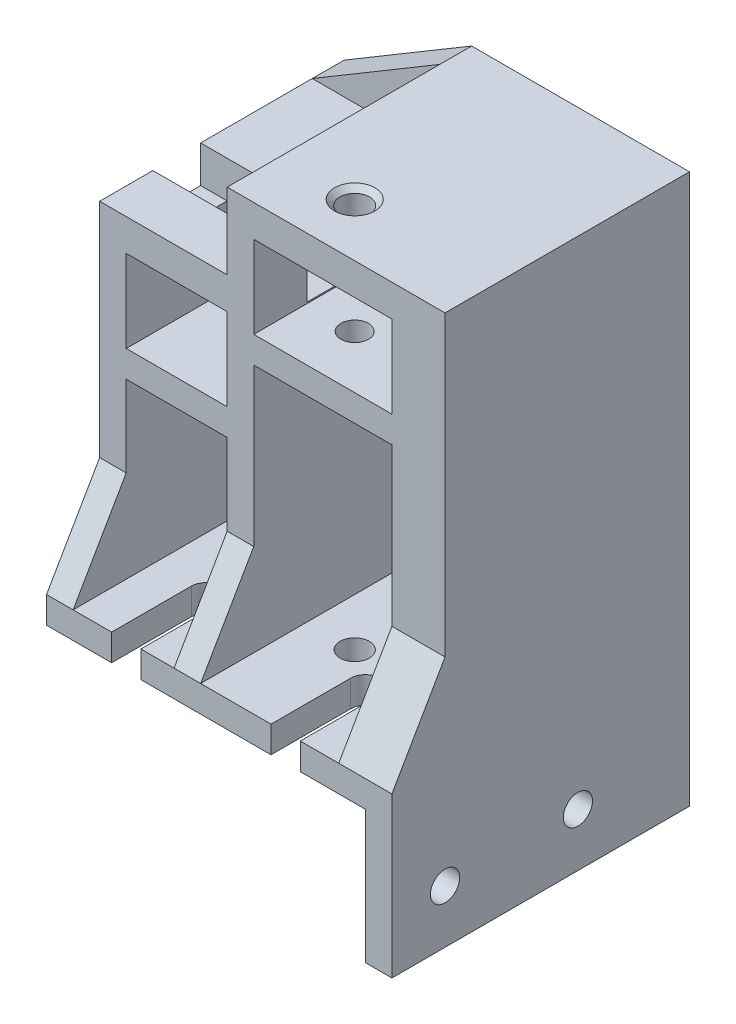
SolidWorks part; units mm, degrees
material "PET"
ref_plane "Front Plane" through (0, 0, 0) normal (0, 0, 1) x (1, 0, 0)
ref_plane "Top Plane" through (0, 0, 0) normal (0, 1, 0) x (1, 0, 0)
ref_plane "Right Plane" through (0, 0, 0) normal (1, 0, 0) x (0, 0, -1)
sketch "Sketch1" plane through (0, 0, 0) normal (0, 0, 1) x (1, 0, 0)
  line L0 (0, 0) -> (0, 64.1)
  line L1 (24, 78.4) -> (60, 78.4)
  line L2 (60, 78.4) -> (60, 0)
  line L4 (5, 5) -> (5, 37.6)
  line L6 (55, 72.4) -> (55, 56.9)
  line L7 (0, 64.1) -> (24, 64.1)
  line L9 (24, 58.1) -> (5, 58.1)
  line L10 (5, 42.6) -> (24, 42.6)
  line L11 (5, 5) -> (24, 5)
  line L12 (24, 37.6) -> (5, 37.6)
  line L13 (55, 56.9) -> (29, 56.9)
  line L14 (5, 42.6) -> (5, 58.1)
  line L15 (29, 51.9) -> (55, 51.9)
  line L18 (55, 51.9) -> (55, 5)
  line L20 (24, 64.1) -> (24, 58.1) construction
  line L21 (29, 56.9) -> (29, 72.4)
  line L22 (24, 64.1) -> (24, 78.4)
  line L23 (29, 72.4) -> (55, 72.4)
  line L24 (29, 51.9) -> (29, 5)
  line L25 (24, 58.1) -> (24, 42.6)
  line L27 (60, 0) -> (0, 0)
  line L28 (24, 37.6) -> (24, 5)
  line L29 (29, 5) -> (55, 5)
  point P20 (14, 42.6)
  point P22 (37, 56.9)
  dimension "D2" = 5
  dimension "D3" = 5
  dimension "D4" = 6
  dimension "D5" = 15.5
  dimension "D6" = 5
  dimension "D7" = 42.6
  dimension "D8" = 15.5
  dimension "D9" = 26
  dimension "D10" = 5
  dimension "D11" = 5
  dimension "D12" = 23
  dimension "D13" = 19
  dimension "D14" = 5
  dimension "D15" = 6
  dimension "D16" = 56.9
  dimension "D19" = 9
extrude "Boss-Extrude1" add sketch "Sketch1" along normal blind 50 contours L22 L7 L0 L4 L12 L10 L14 L9 L15 L18 L2 L1 L21 L23 L6 L13 region at (0.9872, 32.05, 0)
sketch "Sketch2" plane through (0, 78.4, 0) normal (0, 1, 0) x (1, 0, 0)
  line L0 (24, -50) -> (60, -50) construction
  line L1 (60, -50) -> (60, 0) construction
  line L3 (0, 0) -> (24, 0) construction
  circle A0 centre (15, -15) radius 2.6
  circle A1 centre (38, -30) radius 2.6
  dimension "D1" = 23
  dimension "D2" = 5.2
  dimension "D3" = 5.2
  dimension "D4" = 22
  dimension "D5" = 20
  dimension "D6" = 15
extrude "Cut-Extrude1" cut sketch "Sketch2" against normal up to surface (40.8 mm away) up to face at (14.5, 37.6, 25)
sketch "Sketch3" plane through (29, 0, 0) normal (1, 0, 0) x (0, 0, -1)
  line L1 (-21, 72.4) -> (-30, 72.4)
  line L2 (-21, 72.4) -> (-21, 57.15)
  line L3 (-21, 57.15) -> (-30, 57.15)
  line L4 (-30, 72.4) -> (-30, 57.15)
  line L5 (0, 78.4) -> (0, 0) construction
  line L6 (-50, 72.4) -> (0, 72.4) construction
  dimension "D2" = 21
  dimension "D3" = 15.25
  dimension "D4" = 9
extrude "Cut-Extrude2" cut sketch "Sketch3" against normal up to next
sketch "Sketch4" plane through (5, 0, 0) normal (1, 0, 0) x (0, 0, -1)
  line L2 (-5, 42.6) -> (-5, 57.85)
  line L3 (-5, 57.85) -> (-15, 57.85)
  line L4 (-15, 42.6) -> (-15, 57.85)
  line L5 (0, 78.4) -> (0, 0) construction
  line L6 (-5, 42.6) -> (-15, 42.6)
  line L7 (-50, 42.6) -> (0, 42.6) construction
  dimension "D1" = 5
  dimension "D2" = 10
  dimension "D3" = 15.25
extrude "Cut-Extrude3" cut sketch "Sketch4" against normal through all
sketch "Sketch6" plane through (0, 78.4, 0) normal (0, 1, 0) x (1, 0, 0)
  circle A0 centre (15, -15) radius 2.8
  circle A1 centre (38, -30) radius 2.8
  dimension "D1" = 5.6
  dimension "D2" = 5.6
extrude "Cut-Extrude4" cut sketch "Sketch6" against normal up to next
ref_axis "Axis1" through (38, 72.4, 30) along (0, 1, 0)
ref_plane "Plane1" through (38, 0, 0) normal (1, 0, 0) x (0, 0, -1)
chamfer "Chamfer1" distance 1 angle 45 2 edges at (38, 78.4, 32.8) (12.2, 64.1, 15)
sketch "Sketch7" plane through (0, 0, 0) normal (0, -1, 0) x (1, 0, 0)
  line L0 (15, 50) -> (15, 0) construction
  line L1 (60, 50) -> (0, 50) construction
  line L2 (60, 0) -> (0, 0) construction
  line L3 (45, 50) -> (45, 0) construction
  line L5 (0, 50) -> (0, 0) construction
  line L7 (0, 15) -> (60, 15) construction
  line L8 (0, 35) -> (60, 35) construction
  line L9 (60, 50) -> (60, 0) construction
  line L10 (12.25, 35) -> (12.25, 50)
  line L11 (60, 50) -> (0, 50) construction
  line L12 (17.75, 35) -> (17.75, 50)
  line L13 (17.75, 50) -> (12.25, 50)
  line L14 (42.25, 35) -> (42.25, 50)
  line L15 (47.75, 35) -> (47.75, 50)
  line L16 (47.75, 50) -> (42.25, 50)
  arc A0 (12.25, 35) -> (17.75, 35) centre (15, 35) ccw
  arc A1 (42.25, 35) -> (47.75, 35) centre (45, 35) ccw
  circle A2 centre (15, 15) radius 3.3
  circle A3 centre (45, 15) radius 3.3
  dimension "D5" = 5.5
  dimension "D6" = 6.6
  dimension "D7" = 5.5
  dimension "D8" = 6.6
  dimension "D1" = 15
  dimension "D2" = 15
  dimension "D3" = 15
  dimension "D4" = 15
extrude "Cut-Extrude5" cut sketch "Sketch7" against normal up to next
sketch "Sketch8" plane through (0, 5, 0) normal (0, 1, 0) x (1, 0, 0)
  circle A0 centre (38, -30) radius 2.75
  dimension "D1" = 5.5
extrude "Cut-Extrude6" cut sketch "Sketch8" against normal through all
sketch "Sketch9" plane through (0, 0, 0) normal (0, 0, -1) x (-1, 0, 0)
  line L5 (-55, 27) -> (-55, 5)
  line L7 (-60, 0) -> (0, 0) construction
  line L8 (-60, 0) -> (-60, 78.4)
  line L9 (-29, 51.9) -> (-29, 5) construction
  line L10 (-5, 5) -> (-5, 37.6) construction
  line L13 (-55, 27) -> (-29, 27)
  line L17 (-24, 27) -> (-5, 27)
  line L19 (-55, 5) -> (-29, 5)
  line L20 (-29, 5) -> (-29, 27)
  line L21 (-60, 78.4) -> (-24, 78.4)
  line L22 (-24, 78.4) -> (0, 64.1)
  line L23 (0, 64.1) -> (0, 0)
  line L25 (-24, 27) -> (-24, 5)
  line L26 (-24, 5) -> (-5, 5)
  line L27 (-5, 5) -> (-5, 27)
  line L28 (-24, 58.1) -> (-24, 42.6)
  line L29 (-24, 42.6) -> (-5, 42.6)
  line L30 (-5, 42.6) -> (-5, 58.1)
  line L31 (-5, 58.1) -> (-24, 58.1)
  line L32 (-55, 72.4) -> (-55, 56.9)
  line L33 (-55, 56.9) -> (-29, 56.9)
  line L34 (-29, 56.9) -> (-29, 72.4)
  line L35 (-29, 72.4) -> (-55, 72.4)
  line L36 (-60, 0) -> (-60, -25)
  line L37 (-60, -25) -> (0, -25)
  line L38 (0, -25) -> (0, 0)
  line L39 (-45, -12.5) -> (-15, -12.5) construction
  circle A0 centre (-45, -12.5) radius 2.75
  circle A1 centre (-15, -12.5) radius 2.75
  dimension "D3" = 15
  dimension "D4" = 12.5
  dimension "D6" = 5.5
  dimension "D7" = 5.5
  dimension "D1" = 27
  dimension "D2" = 25
  dimension "D5" = 30
extrude "Boss-Extrude2" add sketch "Sketch9" along normal blind 6
sketch "Sketch10" plane through (60, 0, 0) normal (1, 0, 0) x (0, 0, -1)
  line L0 (-50, 5) -> (-40, 22.3205)
  line L1 (-50, 78.4) -> (-50, 0) construction
  line L2 (-40, 22.3205) -> (-40, 78.4)
  line L3 (-50, 78.4) -> (6, 78.4) construction
  line L4 (-40, 78.4) -> (-50, 78.4)
  line L5 (-50, 78.4) -> (-50, 5)
  line L6 (-50, 0) -> (0, 0) construction
  dimension "D1" = 10
  dimension "D2" = 150
  dimension "D3" = 5
extrude "Cut-Extrude7" cut sketch "Sketch10" against normal through all
sketch "Sketch11" plane through (60, 0, 0) normal (1, 0, 0) x (0, 0, -1)
  line L0 (-40, 78.4) -> (-40, 22.3205)
  line L1 (-40, 22.3205) -> (-50, 5)
  line L2 (-50, 5) -> (-50, -25)
  line L3 (-50, -25) -> (6, -25)
  line L4 (6, -25) -> (6, 78.4)
  line L5 (6, 78.4) -> (-40, 78.4)
  line L6 (-50, -15) -> (0, -15) construction
  line L7 (-50, 0) -> (0, 0) construction
  line L8 (0, 0) -> (0, -25) construction
  circle A0 centre (-40, -15) radius 2.75
  circle A1 centre (-15, -15) radius 2.75
  dimension "D2" = 5.5
  dimension "D3" = 5.5
  dimension "D4" = 10
  dimension "D5" = 15
  dimension "D1" = 15
extrude "Boss-Extrude3" add sketch "Sketch11" along normal blind 5
sketch "Sketch12" plane through (0, 0, -6) normal (0, 0, -1) x (-1, 0, 0)
  line L0 (0, 64.1) -> (40, 0)
  line L1 (40, 0) -> (40, -25)
  line L2 (40, -25) -> (0, -25)
  line L3 (0, -25) -> (0, 64.1)
  line L6 (-65, -25) -> (0, -25) construction
  line L7 (0, 0) -> (40, 0) construction
  circle A0 centre (30, -15) radius 2.75
  dimension "D2" = 15
  dimension "D3" = 5.5
  dimension "D4" = 10
  dimension "D1" = 40
extrude "Boss-Extrude4" add sketch "Sketch12" against normal blind 6
